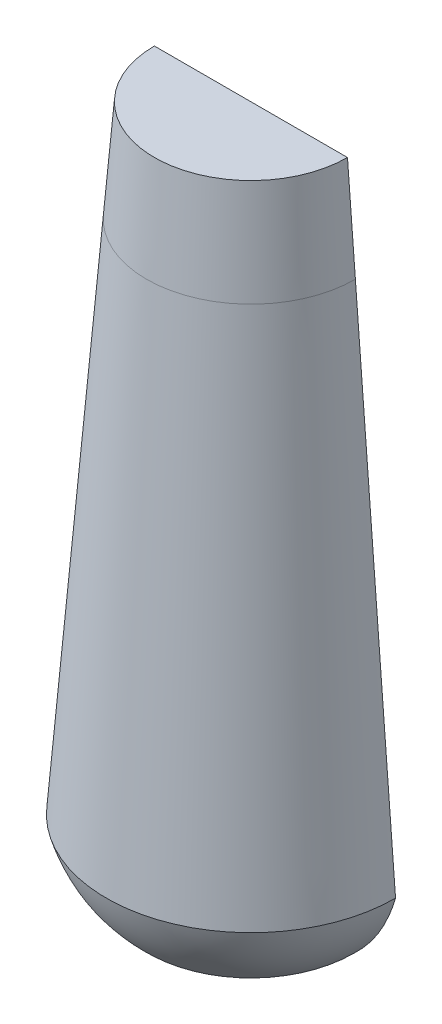
SolidWorks part; units mm, degrees
ref_plane "Front Plane" through (0, 0, 0) normal (0, 0, 1) x (1, 0, 0)
ref_plane "Top Plane" through (0, 0, 0) normal (0, 1, 0) x (1, 0, 0)
ref_plane "Right Plane" through (0, 0, 0) normal (1, 0, 0) x (0, 0, -1)
sketch "Sketch1" plane through (0, 0, 0) normal (0, 0, 1) x (1, 0, 0)
  line L0 (27.686, 0) -> (22.606, 0)
  line L1 (22.606, 0) -> (22.606, 1.8288)
  line L2 (28.829, 4.191) -> (22.606, 4.191)
  line L3 (22.606, 4.191) -> (22.606, 5.8928)
  line L4 (22.606, 5.8928) -> (30.607, 5.8928)
  line L5 (36.5429, 18.669) -> (0, 18.669)
  line L6 (0, 18.669) -> (0, 185.547)
  line L7 (0, 185.547) -> (26.0985, 185.547)
  line L8 (26.0985, 185.547) -> (39.0906, 18.669)
  line L9 (36.5429, 18.669) -> (35.5415, 31.5318) construction
  line L10 (27.686, 0) -> (-4.9317, -30.4165) construction
  line L11 (39.0906, 18.669) -> (57.9001, 81.973) construction
  line L12 (34.3825, 10.171) -> (26.8315, 1.6146) construction
  line L13 (30.8955, 5.835) -> (26.7625, 2.547) construction
  line L14 (22.606, 1.8288) -> (0, 1.8288) construction
  spline S0 degree 3 poles (27.686, 0) (33.0192, 4.9733) (36.7329, 10.7342) (39.0906, 18.669) knots 0 0 0 0 1 1 1 1
  spline S1 degree 3 poles (22.606, 1.8288) (25.0412, 1.8288) (27.1069, 2.821) (28.829, 4.191) knots 0 0 0 0 0.286843 0.286843 0.286843 0.286843
  spline S2 degree 2 poles (30.607, 5.8928) (35.3264, 11.2406) (36.5429, 18.669) knots 0.392904 0.392904 0.392904 1 1 1
  dimension "D1" = 185.547
  dimension "D2" = 39.0906
  dimension "D3" = 18.669
  dimension "D4" = 22.606
  dimension "D5" = 5.08
  dimension "D6" = 1.8288
  dimension "D7" = 2.3622
  dimension "D8" = 6.223
  dimension "D9" = 1.7018
  dimension "D10" = 8.001
  dimension "D11" = 26.0985
  dimension "D12" = 2.54
  dimension "D13" = 43
  dimension "D14" = 21
revolve "Revolve1" add sketch "Sketch1" angle 180 about L6 reverse direction yes
sketch "Sketch2" plane through (0, 185.547, 0) normal (0, 1, 0) x (1, 0, 0)
  line L0 (-23.3045, -1.778) -> (23.3045, -1.778)
  line L1 (23.3045, -1.778) -> (23.3045, -5.842)
  line L2 (23.3045, -5.842) -> (25.4362, -5.842)
  line L3 (25.4362, -5.842) -> (28.0363, -5.842)
  line L4 (-23.3045, -1.778) -> (-23.3045, -5.842)
  line L5 (-23.3045, -5.842) -> (-25.4362, -5.842)
  line L6 (-25.4362, -5.842) -> (-28.0363, -5.842)
  arc A1 (-26.0985, 0) -> (26.0985, 0) centre (0, 0) ccw construction
  arc A2 (-28.6385, 0) -> (28.6385, 0) centre (0, 0) ccw
  arc A3 (-28.0363, -5.842) -> (28.0363, -5.842) centre (0, 0) ccw
  point P6 (0, -1.778)
  dimension "D1" = 2.54
  dimension "D2" = 46.609
  dimension "D3" = 4.064
  dimension "D4" = 5.842
  dimension "D5" = 2.1317
sketch "Sketch3" plane through (0, 0, 0) normal (0, 0, 1) x (1, 0, 0)
  line L0 (-39.0906, 158.115) -> (39.0906, 158.115)
  dimension "D1" = 158.115
split line "Split Line1"
ref_plane "Plane1" through (0, 158.115, 0) normal (0, 1, 0) x (1, 0, 0)
sketch "Sketch4" plane through (0, 158.115, 0) normal (0, 1, 0) x (1, 0, 0)
  line L0 (-25.4914, -1.778) -> (25.4914, -1.778)
  line L1 (25.4914, -1.778) -> (25.4914, -5.842)
  line L2 (25.4914, -5.842) -> (27.6232, -5.842)
  line L3 (27.6232, -5.842) -> (30.2146, -5.842)
  line L4 (-25.4914, -1.778) -> (-25.4914, -5.842)
  line L5 (-25.4914, -5.842) -> (-27.6232, -5.842)
  line L6 (-27.6232, -5.842) -> (-30.2146, -5.842)
  arc A1 (-28.2342, 0) -> (28.2342, 0) centre (0, 0) ccw construction
  arc A2 (-30.7742, 0) -> (30.7742, 0) centre (0, 0) ccw
  arc A3 (-30.2146, -5.842) -> (30.2146, -5.842) centre (0, 0) ccw
  point P6 (0, -1.778)
  dimension "D2" = 4.064
  dimension "D3" = 5.842
  dimension "D4" = 2.1317
  dimension "D1" = 2.54
equation "\"D2@Sketch4\"= \"D3@Sketch2\""
equation "\"D3@Sketch4\"= \"D4@Sketch2\""
equation "\"D4@Sketch4\"= \"D5@Sketch2\""
